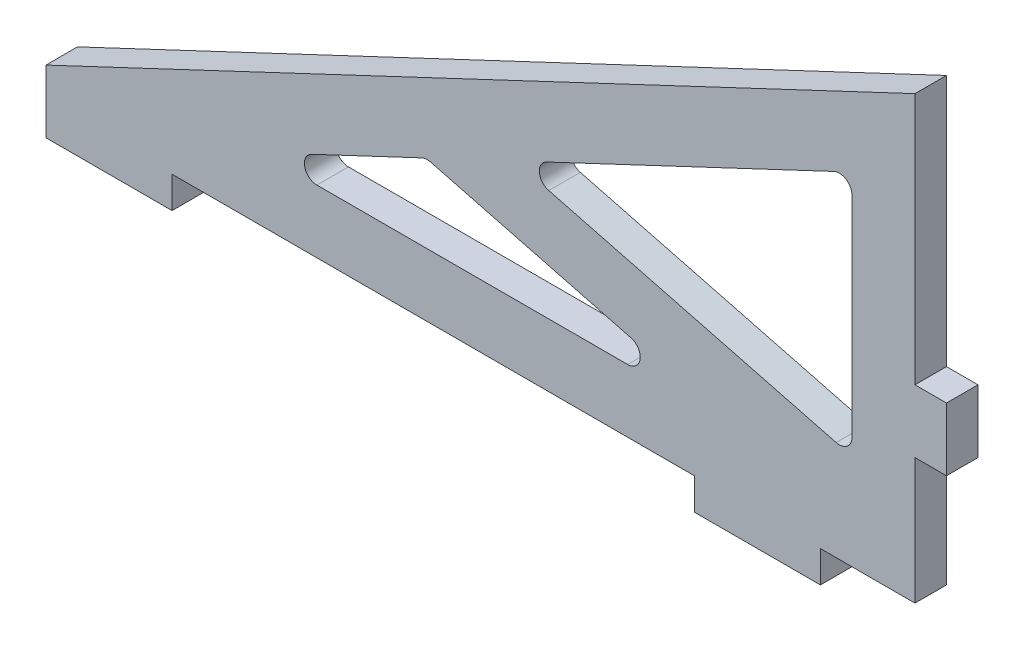
SolidWorks part; units mm, degrees
ref_plane "Front Plane" through (0, 0, 0) normal (0, 0, 1) x (1, 0, 0)
ref_plane "Top Plane" through (0, 0, 0) normal (0, 1, 0) x (1, 0, 0)
ref_plane "Right Plane" through (0, 0, 0) normal (1, 0, 0) x (0, 0, -1)
sketch "Sketch2" plane through (0, 0, 0) normal (0, 0, 1) x (1, 0, 0)
  line L0 (-96.5832, 148.308) -> (78.5, 230.8615)
  line L1 (78.5, 230.8615) -> (84.85, 230.8615) construction
  line L2 (84.85, 230.8615) -> (84.85, 180.058) construction
  line L4 (-121.9832, 135.608) -> (-121.9832, 141.958) construction
  line L5 (84.85, 167.358) -> (84.85, 141.958) construction
  line L6 (84.85, 180.058) -> (78.5, 180.058)
  line L8 (84.85, 167.358) -> (78.5, 167.358)
  line L9 (78.5, 180.058) -> (78.5, 167.358) construction
  line L10 (-96.5832, 135.608) -> (-96.5832, 148.308) construction
  line L13 (-71.1832, 141.958) -> (-71.1832, 135.608)
  line L15 (34.05, 135.608) -> (34.05, 141.958)
  line L17 (59.45, 141.958) -> (59.45, 135.608)
  line L19 (-96.5832, 135.608) -> (-121.9832, 135.608) construction
  line L20 (-96.5832, 141.958) -> (-96.5832, 135.608)
  line L21 (-96.5832, 141.958) -> (-96.5832, 148.308)
  line L22 (-96.5832, 135.608) -> (-71.1832, 135.608)
  line L23 (-71.1832, 141.958) -> (34.05, 141.958)
  line L24 (34.05, 135.608) -> (59.45, 135.608)
  line L25 (59.45, 141.958) -> (78.5, 141.958)
  line L26 (78.5, 167.358) -> (78.5, 141.958)
  line L27 (84.85, 167.358) -> (84.85, 180.058)
  line L28 (78.5, 180.058) -> (78.5, 230.8615)
  point P6 (203.2, 5.8305)
  point P22 (-118.35, 141.958)
  dimension "D1" = 6.35
  dimension "D2" = 6.35
  dimension "D3" = 6.35
  dimension "D4" = 12.7
  dimension "D5" = 6.35
  dimension "D6" = 25.4
  dimension "D7" = 25.4
  dimension "D8" = 25.4
  dimension "D9" = 25.4
  dimension "D10" = 6.35
  dimension "D11" = 25.4
extrude "Boss-Extrude1" add sketch "Sketch2" along normal blind 6.35
sketch "Sketch3" plane through (0, 0, 6.35) normal (0, 0, 1) x (1, 0, 0)
  line L0 (-53.3371, 154.658) -> (65.8, 210.8323)
  line L1 (65.8, 210.8323) -> (65.8, 154.658)
  line L2 (65.8, 154.658) -> (-53.3371, 154.658)
  line L3 (78.5, 230.8615) -> (-96.5832, 148.308) construction
  line L4 (-71.1832, 141.958) -> (34.05, 141.958) construction
  line L6 (65.8, 154.658) -> (-19.3713, 176.756) construction
  line L7 (64.2053, 148.5115) -> (-20.9661, 170.6095)
  line L8 (67.3947, 160.8045) -> (-17.7766, 182.9025)
  line L9 (78.5, 180.058) -> (78.5, 230.8615) construction
  arc A0 (64.2053, 148.5115) -> (67.3947, 160.8045) centre (65.8, 154.658) ccw
  arc A1 (-17.7766, 182.9025) -> (-20.9661, 170.6095) centre (-19.3713, 176.756) ccw
  point P10 (23.2143, 165.707)
  point P15 (122.5424, 38.8398)
  point P16 (124.2169, 40.634)
  point P17 (154.5054, 110.6588)
  point P18 (0, 0)
  point P19 (-19.3713, 176.756)
  dimension "D4" = 6.35
  dimension "D1" = 12.7
  dimension "D2" = 12.7
  dimension "D3" = 12.7
extrude "Cut-Extrude1" cut sketch "Sketch3" against normal through all contours L2 L7 L0 | L8 L1 L0 region at (-10.9488, 159.8937, 6.35) region at (43.175, 183.6264, 6.35)
fillet "Fillet1" radius 2.54 6 edges at (65.8, 210.8323, 3.175) (-2.0749, 178.8286, 3.175) (-20.0245, 170.3652, 3.175) (40.5151, 154.658, 3.175) (-53.3371, 154.658, 3.175) (65.8, 161.2182, 3.175)
